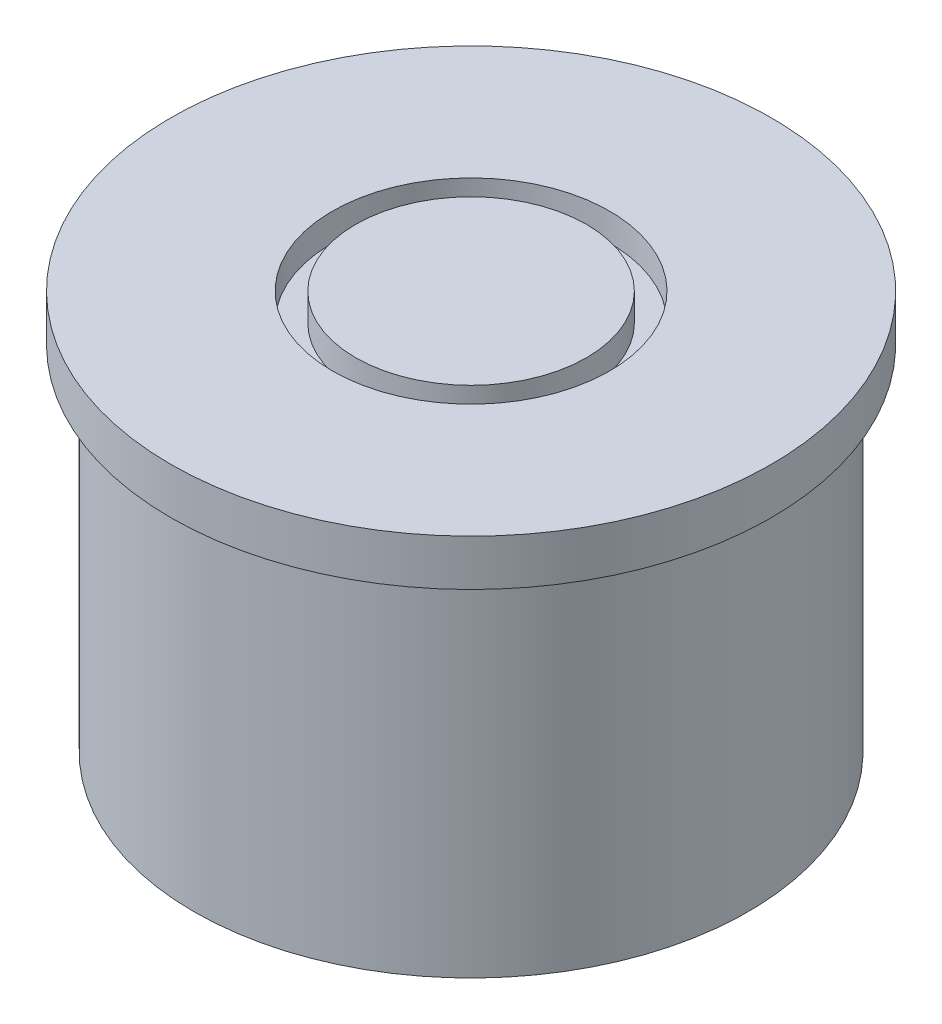
SolidWorks part; units mm, degrees
ref_plane "Front Plane" through (0, 0, 0) normal (0, 0, 1) x (1, 0, 0)
ref_plane "Top Plane" through (0, 0, 0) normal (0, 1, 0) x (1, 0, 0)
ref_plane "Right Plane" through (0, 0, 0) normal (1, 0, 0) x (0, 0, -1)
sketch "Sketch1" plane through (0, 0, 0) normal (0, 1, 0) x (1, 0, 0)
  circle A0 centre (0, 0) radius 32.5
  circle A1 centre (0, 0) radius 30
  dimension "D1" = 65
  dimension "D2" = 60
extrude "Boss-Extrude8" add sketch "Sketch1" against normal blind 43.19 contours A1 region at (0, 0, 0)
extrude "Boss-Extrude10" add sketch "Sketch1<9>" against normal blind 5
sketch "Sketch1<9>" plane through (0, 0, 0) normal (0, 1, 0) x (1, 0, 0) same geometry as "Sketch1"
sketch "Sketch2" plane through (0, -43.19, 0) normal (0, -1, 0) x (1, 0, 0)
  circle A0 centre (0, 0) radius 6
  circle A1 centre (0, 0) radius 8
  dimension "D1" = 16
  dimension "D2" = 12
extrude "Cut-Extrude1" cut sketch "Sketch2" against normal blind 2
sketch "Sketch3" plane through (0, 0, 0) normal (0, 1, 0) x (1, 0, 0)
  circle A0 centre (0, 0) radius 15
  circle A1 centre (0, 0) radius 12.5
  dimension "D1" = 30
  dimension "D2" = 25
extrude "Cut-Extrude2" cut sketch "Sketch3" against normal blind 3
